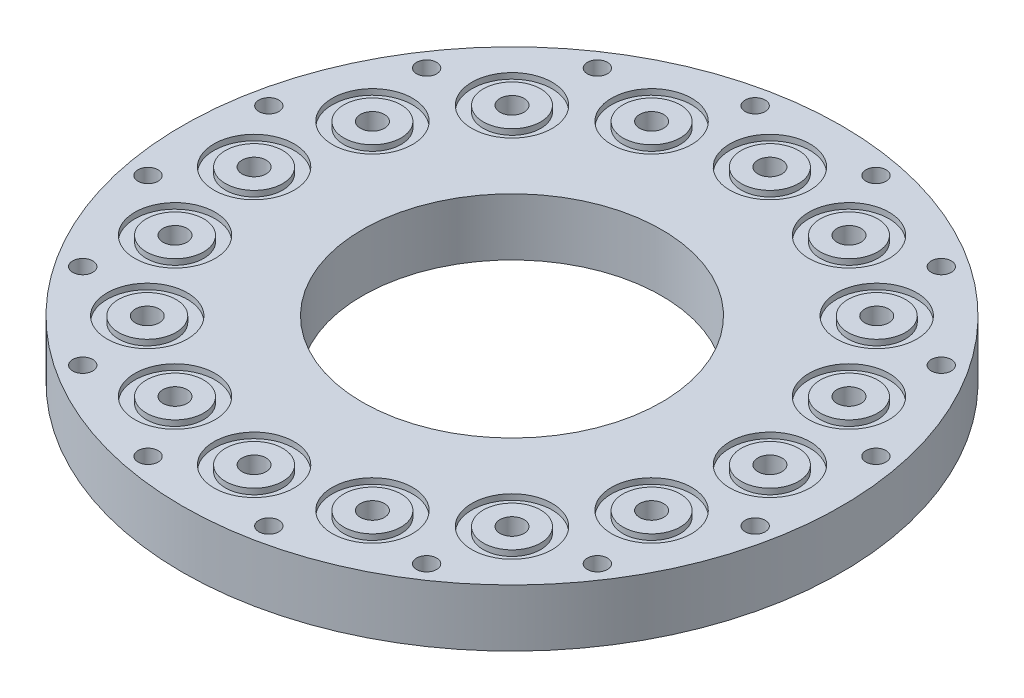
SolidWorks part; units mm, degrees
other "Markup1"
sketch "Sketch3" plane through (-57.5, 10, 57.5) normal (-0.8509, 0.162, 0.4998) x (0.3514, 0.8827, 0.3121)
ref_plane "Front Plane" through (0, 0, 0) normal (0, 0, 1) x (1, 0, 0)
ref_plane "Top Plane" through (0, 0, 0) normal (0, 1, 0) x (1, 0, 0)
ref_plane "Right Plane" through (0, 0, 0) normal (1, 0, 0) x (0, 0, -1)
sketch "Sketch1" plane through (0, 0, 0) normal (0, 1, 0) x (1, 0, 0)
  line L0 (-10.5349, 52.9624) -> (0, 0) construction
  line L1 (0, 0) -> (62.7639, 0) construction
  line L2 (-17.2208, 41.5746) -> (0, 0) construction
  line L3 (0, 0) -> (0, 45) construction
  circle A0 centre (0, 0) radius 57.5
  circle A1 centre (0, 0) radius 54 construction
  circle A2 centre (-10.5349, 52.9624) radius 1.75
  circle A3 centre (10.5349, 52.9624) radius 1.75
  circle A4 centre (30.0008, 44.8994) radius 1.75
  circle A5 centre (44.8994, 30.0008) radius 1.75
  circle A6 centre (52.9624, 10.5349) radius 1.75
  circle A7 centre (52.9624, -10.5349) radius 1.75
  circle A8 centre (44.8994, -30.0008) radius 1.75
  circle A9 centre (30.0008, -44.8994) radius 1.75
  circle A10 centre (10.5349, -52.9624) radius 1.75
  circle A11 centre (-10.5349, -52.9624) radius 1.75
  circle A12 centre (-30.0008, -44.8994) radius 1.75
  circle A13 centre (-44.8994, -30.0008) radius 1.75
  circle A14 centre (0, 0) radius 26.1
  circle A15 centre (0, 0) radius 45 construction
  circle A16 centre (0, 45) radius 2.1
  circle A17 centre (17.2208, 41.5746) radius 2.1
  circle A18 centre (31.8198, 31.8198) radius 2.1
  circle A19 centre (41.5746, 17.2208) radius 2.1
  circle A20 centre (45, 0) radius 2.1
  circle A21 centre (41.5746, -17.2208) radius 2.1
  circle A22 centre (31.8198, -31.8198) radius 2.1
  circle A23 centre (17.2208, -41.5746) radius 2.1
  circle A24 centre (0, -45) radius 2.1
  circle A25 centre (-17.2208, -41.5746) radius 2.1
  circle A26 centre (-31.8198, -31.8198) radius 2.1
  circle A27 centre (-41.5746, -17.2208) radius 2.1
  circle A28 centre (-45, 0) radius 2.1
  circle A29 centre (-41.5746, 17.2208) radius 2.1
  circle A30 centre (-31.8198, 31.8198) radius 2.1
  circle A31 centre (-17.2208, 41.5746) radius 2.1
  circle A32 centre (-52.9624, -10.5349) radius 1.75
  circle A33 centre (-52.9624, 10.5349) radius 1.75
  circle A34 centre (-44.8994, 30.0008) radius 1.75
  circle A35 centre (-30.0008, 44.8994) radius 1.75
  point P31 (0, 0)
  point P55 (0, 0)
  dimension "D1" = 115
  dimension "D2" = 108
  dimension "D3" = 3.5
  dimension "D4" = 52.2
  dimension "D5" = 90
  dimension "D6" = 4.2
  dimension "D9" = 11.25
  dimension "D10" = 11.25
  dimension "D8" = 16
  dimension "D7" = 16
extrude "Boss-Extrude1" add sketch "Sketch1" along normal blind 10
sketch "Sketch2" plane through (0, 10, 0) normal (0, 1, 0) x (1, 0, 0)
  circle A0 centre (0, 0) radius 45 construction
  circle A1 centre (0, 45) radius 7
  circle A2 centre (17.2208, 41.5746) radius 7
  circle A3 centre (31.8198, 31.8198) radius 7
  circle A4 centre (41.5746, 17.2208) radius 7
  circle A5 centre (45, 0) radius 7
  circle A6 centre (41.5746, -17.2208) radius 7
  circle A7 centre (31.8198, -31.8198) radius 7
  circle A8 centre (17.2208, -41.5746) radius 7
  circle A9 centre (0, -45) radius 7
  circle A10 centre (-17.2208, -41.5746) radius 7
  circle A11 centre (-31.8198, -31.8198) radius 7
  circle A12 centre (0, 45) radius 5
  circle A13 centre (17.2208, 41.5746) radius 5
  circle A14 centre (31.8198, 31.8198) radius 5
  circle A15 centre (41.5746, 17.2208) radius 5
  circle A16 centre (45, 0) radius 5
  circle A17 centre (41.5746, -17.2208) radius 5
  circle A18 centre (31.8198, -31.8198) radius 5
  circle A19 centre (17.2208, -41.5746) radius 5
  circle A20 centre (0, -45) radius 5
  circle A21 centre (-17.2208, -41.5746) radius 5
  circle A22 centre (-31.8198, -31.8198) radius 5
  circle A23 centre (-41.5746, -17.2208) radius 5
  circle A24 centre (-45, 0) radius 5
  circle A25 centre (-41.5746, 17.2208) radius 5
  circle A26 centre (-31.8198, 31.8198) radius 5
  circle A27 centre (-17.2208, 41.5746) radius 5
  circle A28 centre (-41.5746, -17.2208) radius 7
  circle A29 centre (-45, 0) radius 7
  circle A30 centre (-41.5746, 17.2208) radius 7
  circle A31 centre (-31.8198, 31.8198) radius 7
  circle A32 centre (-17.2208, 41.5746) radius 7
  point P28 (0, 0)
  point P51 (0, 0)
  dimension "D1" = 14
  dimension "D3" = 10
  dimension "D2" = 16
  dimension "D4" = 16
extrude "Cut-Extrude1" cut sketch "Sketch2" against normal blind 1
